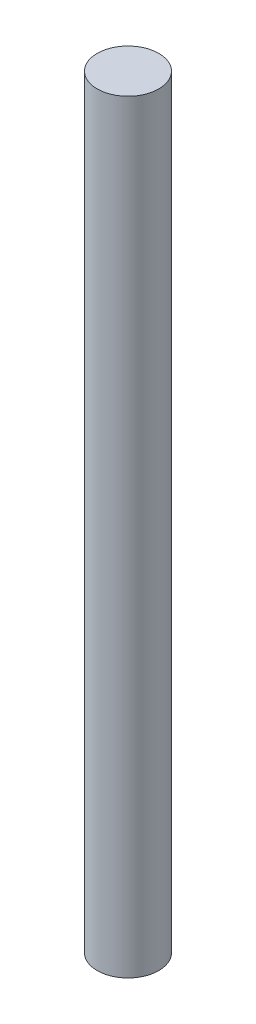
SolidWorks part; units mm, degrees
ref_plane "Front" through (0, 0, 0) normal (0, 0, 1) x (1, 0, 0)
ref_plane "Top" through (0, 0, 0) normal (0, 1, 0) x (1, 0, 0)
ref_plane "Right" through (0, 0, 0) normal (1, 0, 0) x (0, 0, -1)
sketch "Sketch1" plane through (0, 0, 0) normal (0, 1, 0) x (1, 0, 0)
  circle A0 centre (0, 0) radius 1.5875
  dimension "D1" = 3.175
extrude "Boss-Extrude1" add sketch "Sketch1" along normal blind 39.37
